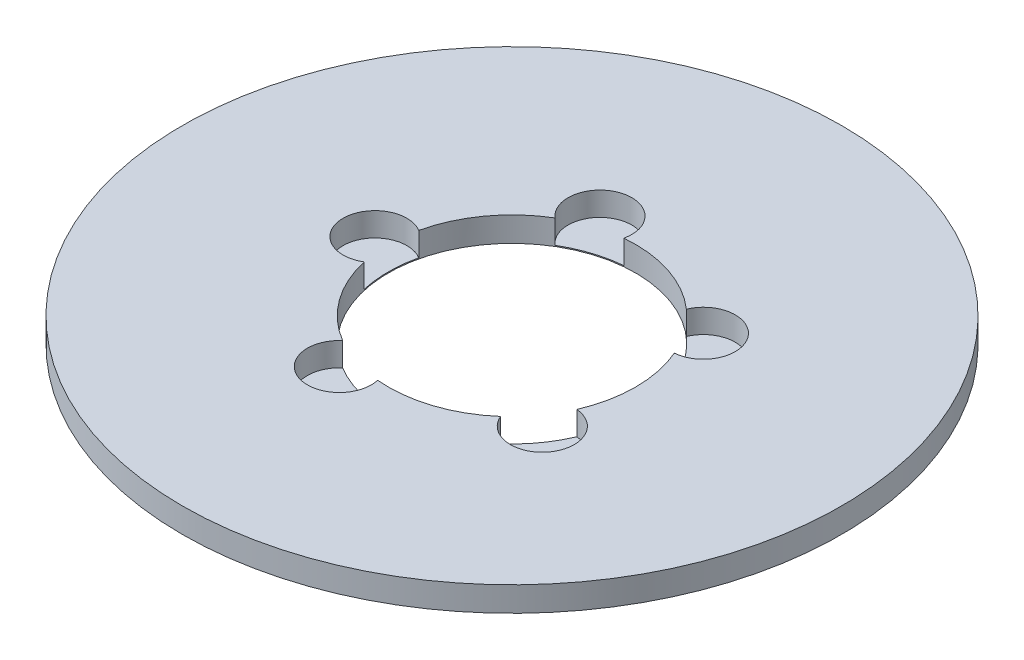
SolidWorks part; units mm, degrees
ref_plane "Front Plane" through (0, 0, 0) normal (0, 0, 1) x (1, 0, 0)
ref_plane "Top Plane" through (0, 0, 0) normal (0, 1, 0) x (1, 0, 0)
ref_plane "Right Plane" through (0, 0, 0) normal (1, 0, 0) x (0, 0, -1)
sketch "Sketch1" plane through (0, 0, 0) normal (0, 1, 0) x (1, 0, 0)
  circle A0 centre (0, 0) radius 80
  dimension "FLANGE_OD" = 160
extrude "Boss-Extrude1" add sketch "Sketch1" along normal blind 6
sketch "Sketch2" plane through (0, 0, 0) normal (0, 1, 0) x (1, 0, 0)
  circle A0 centre (0, 0) radius 30
  dimension "BORE_D" = 60
extrude "Cut-Extrude1" cut sketch "Sketch2" along normal through all
sketch "Sketch3" plane through (0, 6, 0) normal (0, 1, 0) x (1, 0, 0)
  circle A0 centre (0, 0) radius 33.2608 construction
  circle A1 centre (-33.2608, 0) radius 7.7405
  dimension "BOLT_D" = 15.4811
  dimension "BOLT_PCD" = 66.5216
extrude "Cut-Extrude2" cut sketch "Sketch3" against normal blind 5.7553
pattern_circular "CirPattern1" count 5 over 360 about axis through (0, 0, 0) along (0, 1, 0) of "Cut-Extrude2"
